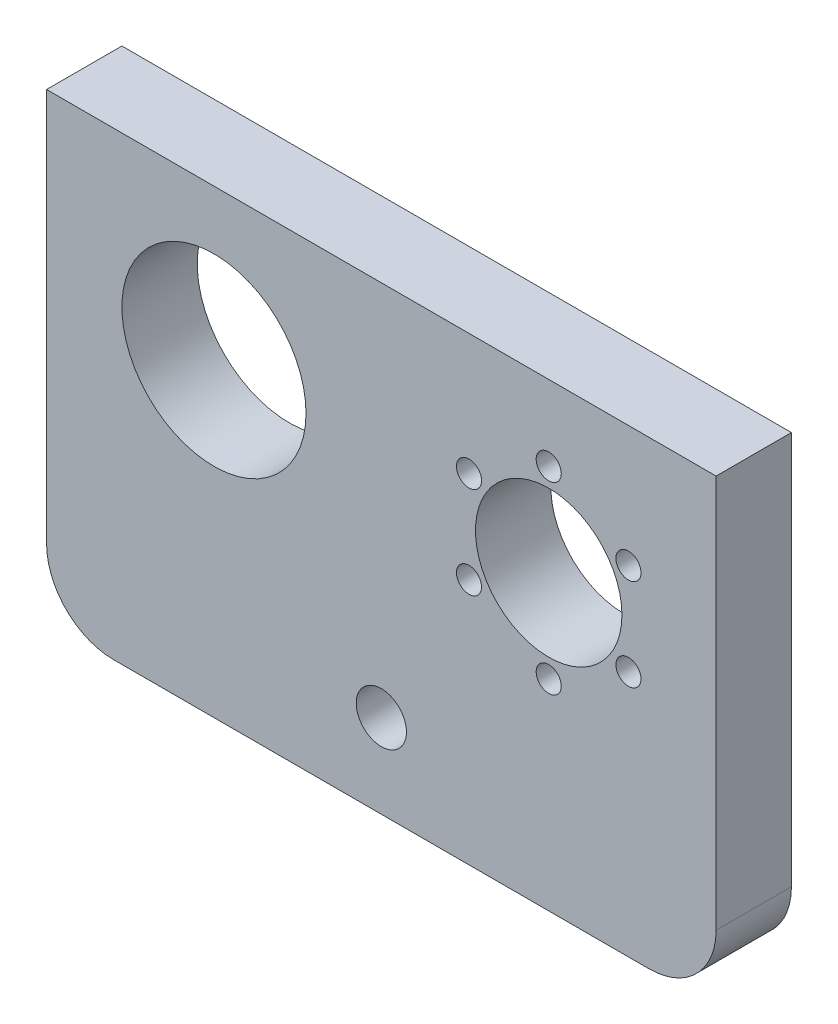
SolidWorks part; units mm, degrees
ref_plane "Front" through (0, 0, 0) normal (0, 0, 1) x (1, 0, 0)
ref_plane "Top" through (0, 0, 0) normal (0, 1, 0) x (1, 0, 0)
ref_plane "Right" through (0, 0, 0) normal (1, 0, 0) x (0, 0, -1)
sketch "Esquisse1" plane through (0, 0, 0) normal (0, 0, 1) x (1, 0, 0)
  line L1 (0, 0) -> (80, 0)
  line L2 (0, 0) -> (0, 55)
  line L3 (0, 55) -> (80, 55)
  line L4 (80, 0) -> (80, 55)
  dimension "D1" = 55
  dimension "D2" = 80
extrude "Boss.-Extru.1" add sketch "Esquisse1" along normal blind 9
sketch "Esquisse2" plane through (0, 0, 9) normal (0, 0, 1) x (1, 0, 0)
  line L0 (20, 55) -> (20, 0) construction
  line L1 (80, 55) -> (0, 55) construction
  line L2 (0, 0) -> (80, 0) construction
  line L4 (60, 35) -> (60, 55) construction
  line L6 (0, 55) -> (0, 0) construction
  circle A0 centre (20, 37) radius 11
  circle A1 centre (60, 35) radius 8.75
  circle A2 centre (60, 46) radius 1.5
  circle A3 centre (69.5263, 40.5) radius 1.5
  circle A4 centre (69.5263, 29.5) radius 1.5
  circle A5 centre (60, 24) radius 1.5
  circle A6 centre (50.4737, 29.5) radius 1.5
  circle A7 centre (50.4737, 40.5) radius 1.5
  point P29 (60, 35)
  dimension "D1" = 22
  dimension "D2" = 18
  dimension "D4" = 17.5
  dimension "D7" = 3
  dimension "D3" = 20
  dimension "D5" = 20
  dimension "D6" = 20
  dimension "D8" = 11
  dimension "D9" = 6
extrude "Enlèv. mat.-Extru.1" cut sketch "Esquisse2" against normal through all
sketch "Esquisse3" plane through (0, 0, 9) normal (0, 0, 1) x (1, 0, 0)
  circle A0 centre (40, 10) radius 3
  circle A1 centre (60, 35) radius 8.75 construction
  dimension "D3" = 6
  dimension "D1" = 25
  dimension "D2" = 20
extrude "Enlèv. mat.-Extru.2" cut sketch "Esquisse3" against normal through all
fillet "Congé1" radius 8 2 edges at (0, 0, 4.5) (80, 0, 4.5)
